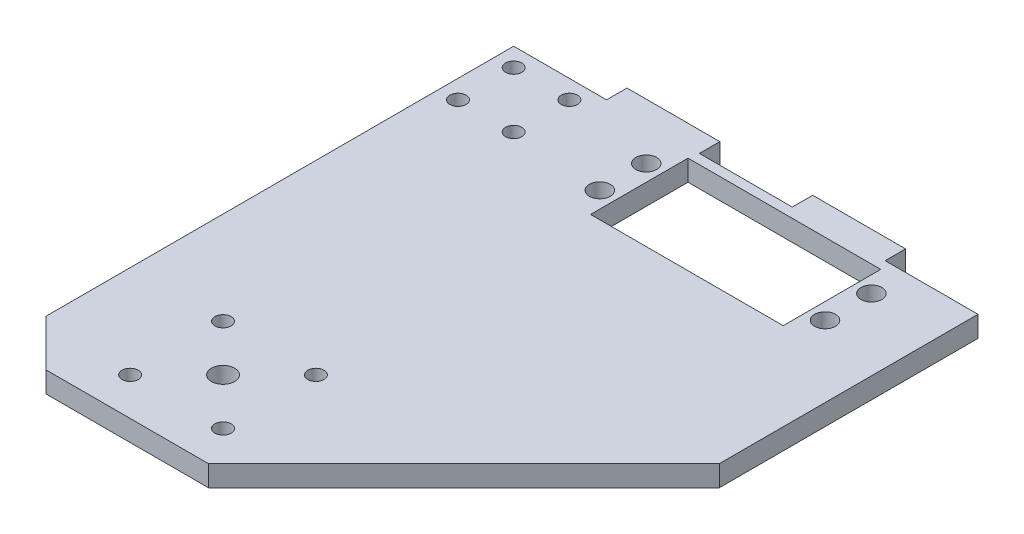
SolidWorks part; units mm, degrees
ref_plane "Front Plane" through (0, 0, 0) normal (0, 0, 1) x (1, 0, 0)
ref_plane "Top Plane" through (0, 0, 0) normal (0, 1, 0) x (1, 0, 0)
ref_plane "Right Plane" through (0, 0, 0) normal (1, 0, 0) x (0, 0, -1)
sketch "Sketch2" plane through (0, 0, 0) normal (0, 1, 0) x (1, 0, 0)
  line L3 (110, 70) -> (-110, 70)
  line L4 (110, 70) -> (110, -70)
  line L5 (110, -70) -> (-110, -70)
  line L6 (-110, 70) -> (-110, -70)
  line L7 (110, 70) -> (-110, -70) construction
  line L8 (110, -70) -> (-110, 70) construction
  point P0 (0, 0)
  dimension "D1" = 220
  dimension "D2" = 140
extrude "Boss-Extrude1" add sketch "Sketch2" along normal blind 4.5
chamfer "Chamfer1" [suppressed] distance 75 angle 40
sketch "Sketch3" plane through (0, 4.5, 0) normal (0, 1, 0) x (1, 0, 0)
  line L0 (0, 70) -> (0, -27) construction
  line L1 (110, 70) -> (-110, 70) construction
  line L2 (0, -27) -> (40.6, -27) construction
  line L3 (40.6, -27) -> (40.6, 53) construction
  circle A0 centre (0, -27) radius 2.5
  circle A1 centre (40.6, 53) radius 2.5
  dimension "D2" = 5
  dimension "D5" = 5
  dimension "D1" = 97
  dimension "D3" = 80
  dimension "D4" = 40.6
extrude "Cut-Extrude1" cut sketch "Sketch3" against normal through all
sketch "Sketch4" plane through (0, 0, 0) normal (0, -1, 0) x (1, 0, 0)
  line L0 (110, 70) -> (110, -70) construction
  line L1 (110, -70) -> (90, -70)
  line L2 (110, -70) -> (110, -65.6)
  line L3 (110, -65.6) -> (90, -65.6)
  line L4 (90, -70) -> (90, -65.6)
  line L5 (110, -70) -> (90, -65.6) construction
  line L6 (110, -65.6) -> (90, -70) construction
  line L7 (0, -70) -> (0, 0) construction
  line L8 (70, -70) -> (50, -70)
  line L9 (70, -70) -> (70, -65.6)
  line L10 (70, -65.6) -> (50, -65.6)
  line L11 (50, -70) -> (50, -65.6)
  line L12 (70, -70) -> (50, -65.6) construction
  line L13 (70, -65.6) -> (50, -70) construction
  line L14 (30, -70) -> (10, -70)
  line L15 (30, -70) -> (30, -65.6)
  line L16 (30, -65.6) -> (10, -65.6)
  line L17 (10, -70) -> (10, -65.6)
  line L18 (30, -70) -> (10, -65.6) construction
  line L19 (30, -65.6) -> (10, -70) construction
  line L20 (-30, -65.6) -> (-10, -70) construction
  line L21 (-30, -70) -> (-10, -65.6) construction
  line L22 (-70, -65.6) -> (-50, -70) construction
  line L23 (-70, -70) -> (-50, -65.6) construction
  line L24 (-110, -65.6) -> (-90, -70) construction
  line L25 (-110, -70) -> (-90, -65.6) construction
  line L26 (-10, -70) -> (-10, -65.6)
  line L27 (-30, -65.6) -> (-10, -65.6)
  line L28 (-30, -70) -> (-30, -65.6)
  line L29 (-30, -70) -> (-10, -70)
  line L30 (-50, -70) -> (-50, -65.6)
  line L31 (-70, -65.6) -> (-50, -65.6)
  line L32 (-70, -70) -> (-70, -65.6)
  line L33 (-70, -70) -> (-50, -70)
  line L34 (-90, -70) -> (-90, -65.6)
  line L35 (-110, -65.6) -> (-90, -65.6)
  line L36 (-110, -70) -> (-110, -65.6)
  line L37 (-110, -70) -> (-90, -70)
  line L38 (0, -70) -> (110, -70) construction
  point P4 (100, -67.8)
  point P29 (-100, -67.8)
  dimension "D1" = 4.4
  dimension "D2" = 20
  dimension "D3" = 3
  dimension "D4" = 70
  dimension "D5" = 20
extrude "Teeth cut" cut sketch "Sketch4" against normal through all
sketch "Sketch5" plane through (0, 0, 0) normal (0, -1, 0) x (1, 0, 0)
  line L0 (-110, 70) -> (110, 70) construction
  line L1 (110, -70.1) -> (70, -70.1)
  line L2 (110, -70.1) -> (110, 70)
  line L3 (110, 70) -> (70, 70)
  line L4 (70, -70.1) -> (70, 45.1242)
  line L5 (110, -70.1) -> (70, 70) construction
  line L6 (110, 70) -> (70, -70.1) construction
  line L7 (-110, -65.6) -> (-110, 70) construction
  line L8 (-30, -70.1) -> (-110, -70.1)
  line L9 (-30, -70.1) -> (-30, 45.1242)
  line L10 (-30, 70) -> (-110, 70)
  line L11 (-110, -70.1) -> (-110, 70)
  line L12 (-30, -70.1) -> (-110, 70) construction
  line L13 (-30, 70) -> (-110, -70.1) construction
  line L14 (110, 70) -> (110, -65.6) construction
  line L15 (-30, 45.1242) -> (-30, 70) construction
  line L16 (-30, 70) -> (70, 70)
  line L17 (-30, 70) -> (-30, 45.1242) construction
  line L18 (-30, 45.1242) -> (70, 45.1242)
  line L19 (70, 70) -> (70, 45.1242) construction
  line L20 (70, 45.1242) -> (70, 70) construction
  point P4 (90, -0.05)
  point P11 (-70, -0.05)
  dimension "D1" = 80
  dimension "D2" = 40
extrude "Trim cut" cut sketch "Sketch5" against normal through all
sketch "Sketch6" plane through (0, 4.5, 0) normal (0, 1, 0) x (1, 0, 0)
  line L0 (-30, 65.6) -> (-30, -45.1242) construction
  line L1 (51.15, 42.5) -> (9.65, 42.5)
  line L2 (51.15, 42.5) -> (51.15, 63.5)
  line L3 (51.15, 63.5) -> (9.65, 63.5)
  line L4 (9.65, 42.5) -> (9.65, 63.5)
  line L5 (51.15, 42.5) -> (9.65, 63.5) construction
  line L6 (51.15, 63.5) -> (9.65, 42.5) construction
  line L7 (-10, 65.6) -> (-30, 65.6) construction
  line L8 (-10, 65.6) -> (-10, 45.6) construction
  line L9 (-10, 45.6) -> (-30, 45.6) construction
  line L10 (-30, 65.6) -> (-30, 45.6) construction
  line L11 (-14, 61.6) -> (-26, 61.6) construction
  line L12 (-26, 61.6) -> (-26, 49.6) construction
  line L13 (-14, 49.6) -> (-26, 49.6) construction
  line L14 (-14, 61.6) -> (-14, 49.6) construction
  circle A0 centre (6.15, 58) radius 2.25
  circle A1 centre (6.15, 48) radius 2.25
  circle A2 centre (54.65, 48) radius 2.25
  circle A3 centre (54.65, 58) radius 2.25
  circle A4 centre (-14, 49.6) radius 1.75
  circle A5 centre (10, -17) radius 1.75
  circle A6 centre (10, -37) radius 1.75
  circle A7 centre (-10, -37) radius 1.75
  circle A8 centre (-10, -17) radius 1.75
  circle A9 centre (-26, 49.6) radius 1.75
  circle A10 centre (-26, 61.6) radius 1.75
  circle A11 centre (-14, 61.6) radius 1.75
  point P24 (30.4, 53)
  dimension "D1" = 4.5
  dimension "D2" = 3.5
  dimension "D3" = 21
  dimension "D4" = 41.5
  dimension "D5" = 20
  dimension "D6" = 4
extrude "Cut-Extrude2" cut sketch "Sketch6" against normal through all
ref_axis "Axis1" through (40.6, 42.5401, -53) along (0, -1, 0)
chamfer "Chamfer4" distance 10 angle 45 1 edges at (-30, 2.25, 45.1242)
chamfer "Chamfer5" distance 55 angle 45 1 edges at (70, 2.25, 45.1242)
